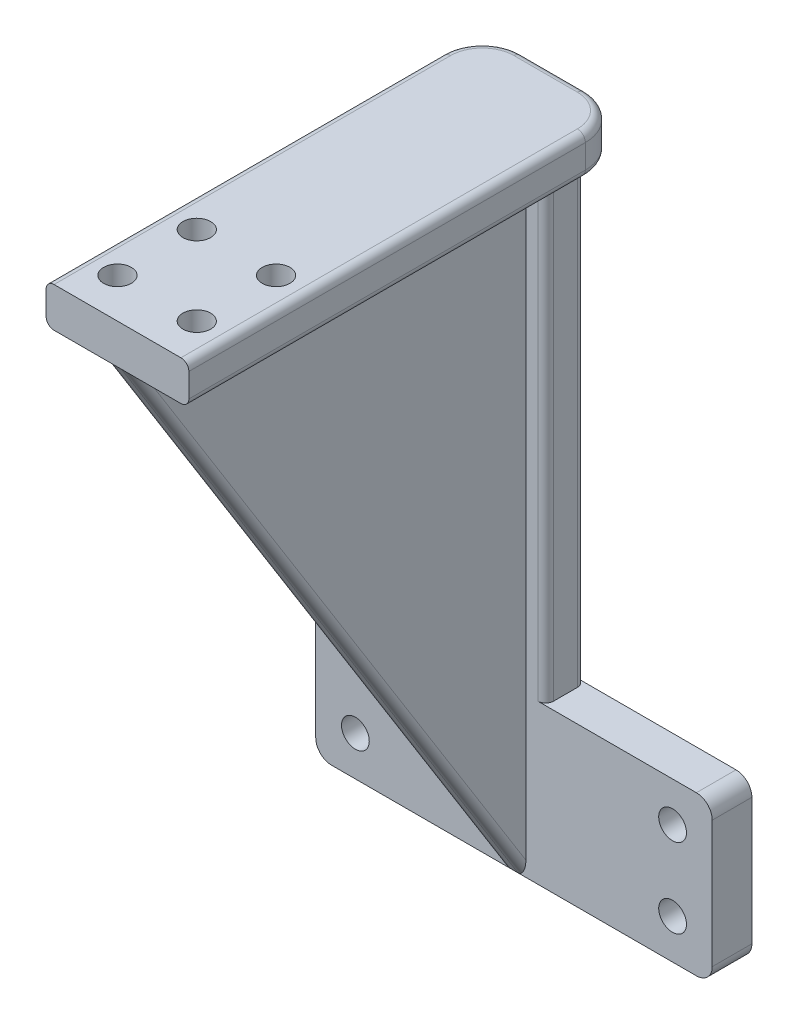
SolidWorks part; units mm, degrees
ref_plane "Front Plane" through (0, 0, 0) normal (0, 0, 1) x (1, 0, 0)
ref_plane "Top Plane" through (0, 0, 0) normal (0, 1, 0) x (1, 0, 0)
ref_plane "Right Plane" through (0, 0, 0) normal (1, 0, 0) x (0, 0, -1)
sketch "Sketch1" plane through (0, 0, 0) normal (0, 0, 1) x (1, 0, 0)
  line L5 (-25, 10) -> (25, 10)
  line L6 (-25, 10) -> (-25, -10)
  line L7 (-25, -10) -> (25, -10)
  line L8 (25, 10) -> (25, -10)
  line L9 (-25, 10) -> (25, -10) construction
  line L10 (-25, -10) -> (25, 10) construction
  circle A0 centre (-20, 5) radius 1.75
  circle A1 centre (-20, -5) radius 1.75
  circle A2 centre (20, -5) radius 1.75
  circle A3 centre (20, 5) radius 1.75
  point P0 (0, 0)
  point P1 (0, 0)
  dimension "D4" = 3.5
  dimension "D1" = 10
  dimension "D2" = 20
  dimension "D3" = 20
  dimension "D5" = 5
  dimension "D6" = 5
  dimension "D7" = 5
extrude "Boss-Extrude1" add sketch "Sketch1" along normal blind 5
sketch "Sketch2" plane through (0, 10, 0) normal (0, 1, 0) x (1, 0, 0)
  line L0 (25, 0) -> (-25, 0) construction
  line L1 (-4, 0) -> (4, 0)
  line L2 (-4, 0) -> (-4, -5)
  line L3 (-4, -5) -> (4, -5)
  line L4 (4, 0) -> (4, -5)
  line L5 (25, -5) -> (-25, -5) construction
  dimension "D1" = 4
  dimension "D2" = 8
extrude "Boss-Extrude2" add sketch "Sketch2" along normal blind 65
sketch "Sketch3" plane through (0, 0, 5) normal (0, 0, 1) x (1, 0, 0)
  line L0 (4, 75) -> (4, 10) construction
  line L1 (-4, 75) -> (4, 75)
  line L2 (-4, 75) -> (-4, 70)
  line L3 (-4, 70) -> (4, 70)
  line L4 (4, 75) -> (4, 70)
  dimension "D1" = 5
extrude "Boss-Extrude3" add sketch "Sketch3" along normal blind 50
sketch "Sketch7" plane through (0, 0, 0) normal (1, 0, 0) x (0, 0, -1)
  line L0 (-55, 75) -> (-55, 70)
  line L1 (-55, 70) -> (-5, -10)
  line L2 (-5, -10) -> (0, -10)
  line L3 (0, -10) -> (0, 10) construction
  line L4 (0, -10) -> (0, 75)
  line L5 (0, 75) -> (-55, 75)
extrude "Boss-Extrude6" add sketch "Sketch7" along normal blind 1.5 and the other way blind 1.5
sketch "Sketch8" plane through (0, 70, 0) normal (0, -1, 0) x (1, 0, 0)
  line L0 (-4, 55) -> (-4, 5) construction
  line L1 (4, 55) -> (4, 5) construction
  line L2 (1.5, 55) -> (4, 55) construction
  circle A0 centre (0, 47) radius 1.75
  circle A1 centre (0, 47) radius 1.75
  circle A2 centre (0, 37) radius 1.75
  circle A3 centre (0, 37) radius 1.75
  circle A4 centre (0, 27) radius 1.75
  circle A5 centre (0, 27) radius 1.75
  dimension "D2" = 3.5
  dimension "D1" = 4
  dimension "D3" = 4
  dimension "D4" = 8
  dimension "D5" = 10
  dimension "D6" = 10
extrude "Cut-Extrude2" [suppressed] cut sketch "Sketch8" against normal up to next
fillet "Fillet4" radius 1 2 edges at (-1.5, 30, 30) (1.5, 30, 30)
fillet "Fillet5" radius 2 4 edges at (25, 10, 2.5) (25, -10, 2.5) (-25, -10, 2.5) (-25, 10, 2.5)
sketch "Sketch14" plane through (-4, 0, 0) normal (-1, 0, 0) x (0, 0, 1)
  line L1 (0, 75) -> (55, 75)
  line L2 (0, 75) -> (0, 70)
  line L3 (0, 70) -> (55, 70)
  line L4 (55, 75) -> (55, 70)
extrude "Boss-Extrude9" add sketch "Sketch14" along normal blind 5
mirror "Mirror1" about plane through (0, 0, 0) normal (1, 0, 0) of "Boss-Extrude9"
sketch "Sketch15" plane through (0, 75, 0) normal (0, 1, 0) x (1, 0, 0)
  line L0 (-9, -55) -> (-9, 0) construction
  line L1 (9, -55) -> (-9, -55) construction
  circle A0 centre (-5, -40) radius 1.75
  circle A1 centre (5, -40) radius 1.75
  circle A2 centre (-5, -50) radius 1.75
  circle A3 centre (5, -50) radius 1.75
  dimension "D1" = 3.5
  dimension "D2" = 10
  dimension "D3" = 4
  dimension "D4" = 5
  dimension "D5" = 10
extrude "Cut-Extrude3" cut sketch "Sketch15" against normal up to next
fillet "Fillet6" radius 5 2 edges at (-9, 72.5, 0) (9, 72.5, 0)
fillet "Fillet10" radius 1 4 edges at (4, 40, 5) (4, 40, 0) (-4, 40, 0) (-4, 40, 5)
fillet "Fillet11" radius 1 8 edges at (-9, 70, 30) (-3.5, 70, 0) (9, 75, 30) (7.5355, 75, 1.4645) (0, 75, 0) (-9, 75, 30) (-7.5355, 70, 1.4645) (-7.5355, 75, 1.4645)
fillet "Fillet14" radius 1 2 edges at (7.5355, 70, 1.4645) (9, 70, 30)
